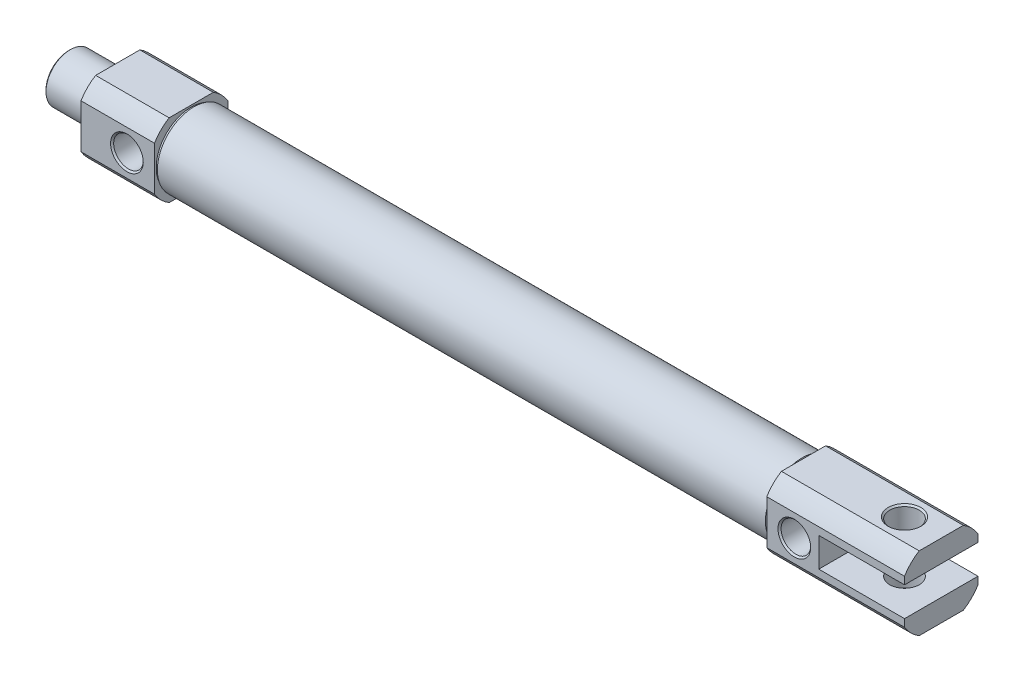
SolidWorks part; units mm, degrees
ref_plane "Front Plane" through (0, 0, 0) normal (0, 0, 1) x (1, 0, 0)
ref_plane "Top Plane" through (0, 0, 0) normal (0, 1, 0) x (1, 0, 0)
ref_plane "Right Plane" through (0, 0, 0) normal (1, 0, 0) x (0, 0, -1)
sketch "Sketch1" plane through (0, 0, 0) normal (1, 0, 0) x (0, 0, -1)
  circle A0 centre (0, 0) radius 5
  circle A1 centre (0, 0) radius 5.97
  dimension "D1" = 10
  dimension "D2" = 11.94
extrude "Boss-Extrude1" add sketch "Sketch1" along normal mid plane 80.4 contours A0 region at (0, 0, 0)
extrude "Boss-Extrude2" add sketch "Sketch1<3>" along normal mid plane 100
sketch "Sketch1<3>" plane through (0, 0, 0) normal (1, 0, 0) x (0, 0, -1) same geometry as "Sketch1"
chamfer "Chamfer1" distance 0.254 angle 60 1 edges at (50, 0, -5.97) first distance on face at (50, 0, -5.97)
chamfer "Chamfer2" distance 0.254 angle 60 1 edges at (-50, 0, -5.97) first distance on face at (-50, 0, -5.97)
sketch "Sketch2" plane through (50, 0, 0) normal (1, 0, 0) x (0, 0, -1)
  line L1 (6, -6) -> (-6, -6)
  line L2 (6, -6) -> (6, 6)
  line L3 (6, 6) -> (-6, 6)
  line L4 (-6, -6) -> (-6, 6)
  line L5 (6, -6) -> (-6, 6) construction
  line L6 (6, 6) -> (-6, -6) construction
  circle A0 centre (0, 0) radius 7
  point P0 (0, 0)
  dimension "D3" = 14
  dimension "D1" = 12
  dimension "D2" = 12
sketch "Sketch3" plane through (50, 0, 0) normal (1, 0, 0) x (0, 0, -1)
  line L0 (-6, 3.6055) -> (-6, -3.6055)
  line L1 (6, 3.6055) -> (6, -3.6055)
  line L2 (-3.6055, 6) -> (3.6055, 6)
  line L3 (-3.6055, -6) -> (3.6055, -6)
  line L4 (6, -6) -> (6, 6) construction
  line L5 (6, 6) -> (-6, 6) construction
  line L6 (-6, -6) -> (-6, 6) construction
  line L7 (6, -6) -> (-6, -6) construction
  arc A0 (-6, 3.6055) -> (-3.6055, 6) centre (0, 0) cw
  arc A1 (6, 3.6055) -> (3.6055, 6) centre (0, 0) ccw
  arc A2 (6, -3.6055) -> (3.6055, -6) centre (0, 0) cw
  arc A3 (-6, -3.6055) -> (-3.6055, -6) centre (0, 0) ccw
  circle A4 centre (0, 0) radius 7 construction
extrude "Boss-Extrude3" add sketch "Sketch3" along normal blind 22.5
sketch "Sketch5" plane through (0, 6, 0) normal (0, 1, 0) x (1, 0, 0)
  line L0 (72.5, 3.6055) -> (72.5, -3.6055) construction
  circle A0 centre (66.5, 0) radius 2.415
  dimension "D2" = 4.8301
  dimension "D1" = 6
extrude "Cut-Extrude2" cut sketch "Sketch5" against normal through all
sketch "Sketch6" plane through (0, 0, 6) normal (0, 0, 1) x (1, 0, 0)
  line L0 (72.5, 3.6055) -> (72.5, -3.6055) construction
  line L1 (58.5, -2.39) -> (72.5, -2.39)
  line L2 (58.5, -2.39) -> (58.5, 2.39)
  line L3 (58.5, 2.39) -> (72.5, 2.39)
  line L4 (72.5, -2.39) -> (72.5, 2.39)
  line L5 (58.5, -2.39) -> (72.5, 2.39) construction
  line L6 (58.5, 2.39) -> (72.5, -2.39) construction
  point P0 (65.5, 0)
  dimension "D1" = 14
  dimension "D2" = 4.78
extrude "Cut-Extrude3" cut sketch "Sketch6" against normal through all
extrude "Boss-Extrude4" add sketch "Sketch3<2>" against normal blind 12 from surface starting at face at (-50, 0, -5.716)
sketch "Sketch3<2>" plane through (50, 0, 0) normal (1, 0, 0) x (0, 0, -1) same geometry as "Sketch3"
sketch "Sketch4" plane through (0, 0, 6) normal (0, 0, 1) x (1, 0, 0)
  line L0 (50, 3.6055) -> (50, -3.6055) construction
  line L1 (-50, 3.6055) -> (-50, -3.6055) construction
  circle A0 centre (54.5001, 0) radius 2.415
  circle A1 centre (-54.5001, 0) radius 2.415
  dimension "D2" = 4.8301
  dimension "D1" = 4.5001
  dimension "D3" = 4.5001
extrude "Cut-Extrude4" cut sketch "Sketch4" against normal blind 6
sketch "Sketch8" plane through (-62, 0, 0) normal (-1, 0, 0) x (0, 0, 1)
  circle A0 centre (0, 0) radius 3.9688
  circle A1 centre (0, 0) radius 2.1827
  dimension "D1" = 4.3655
  dimension "D2" = 7.9375
extrude "Boss-Extrude5" add sketch "Sketch8" along normal blind 8
chamfer "Chamfer5" distance 0.254 angle 45 6 edges at (66.5, -6, 2.415) (66.5, 6, 2.415) (56.9151, 0, 6) (-52.0851, 0, 6) (-70, 0, 3.9688) (-70, 0, 2.1827)
equation "\"D2@Sketch2\"=\"D1@Sketch2\""
